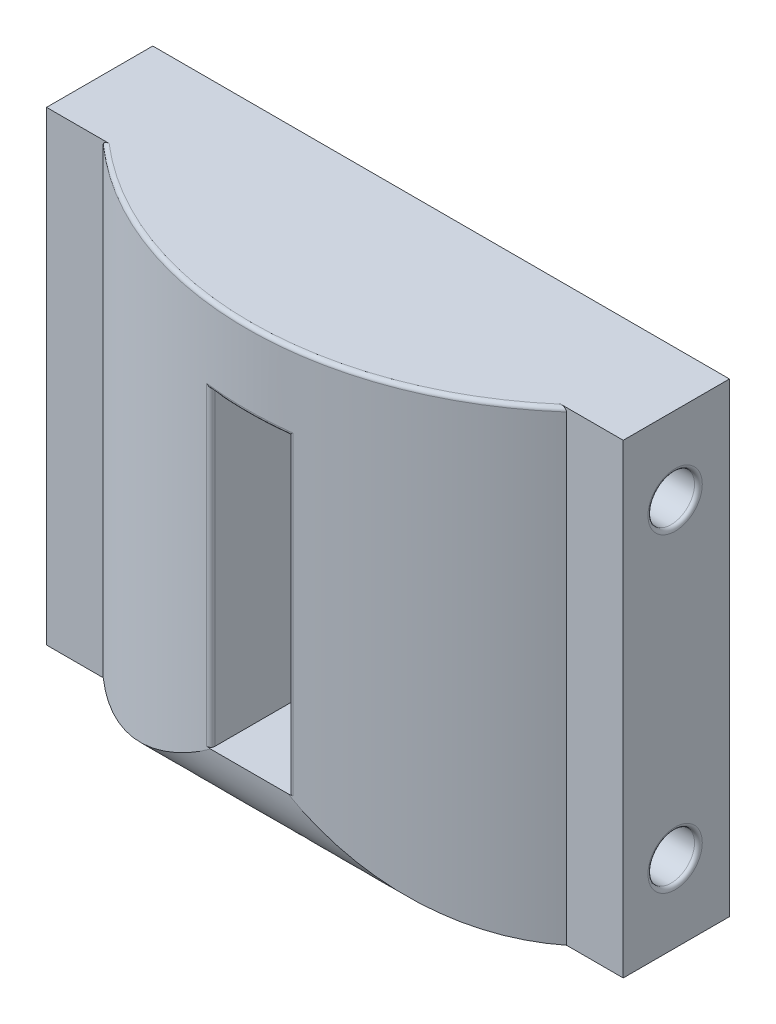
SolidWorks part; units mm, degrees
ref_plane "Front Plane" through (0, 0, 0) normal (0, 0, 1) x (1, 0, 0)
ref_plane "Top Plane" through (0, 0, 0) normal (0, 1, 0) x (1, 0, 0)
ref_plane "Right Plane" through (0, 0, 0) normal (1, 0, 0) x (0, 0, -1)
sketch "Sketch1" plane through (0, 0, 0) normal (0, 0, 1) x (1, 0, 0)
  line L1 (0, 0) -> (29.85, 0)
  line L2 (0, 0) -> (0, 30)
  line L3 (0, 30) -> (29.85, 30)
  line L4 (29.85, 0) -> (29.85, 30)
  dimension "D1" = 29.85
  dimension "D2" = 30
extrude "Boss-Extrude1" add sketch "Sketch1" along normal blind 12.5
sketch "Sketch2" plane through (0, 0, 12.5) normal (0, 0, 1) x (1, 0, 0)
  line L1 (12.425, 25) -> (17.425, 25)
  line L2 (12.425, 25) -> (12.425, 5)
  line L3 (12.425, 5) -> (17.425, 5)
  line L4 (17.425, 25) -> (17.425, 5)
  line L5 (29.85, 30) -> (0, 30) construction
  line L6 (14.925, 30) -> (14.925, 0) construction
  line L7 (0, 0) -> (29.85, 0) construction
  point P4 (14.925, 25)
  dimension "D1" = 5
  dimension "D2" = 20
  dimension "D4" = 5
extrude "Cut-Extrude1" cut sketch "Sketch2" against normal through all
sketch "Sketch4" plane through (29.85, 0, 0) normal (1, 0, 0) x (0, 0, -1)
  line L0 (-12.5, 30) -> (0, 30) construction
  line L1 (0, 0) -> (0, 30) construction
  line L2 (-12.5, 0) -> (0, 0) construction
  circle A0 centre (-3.5, 25) radius 1.5
  circle A1 centre (-3.5, 5) radius 1.5
  dimension "D1" = 3
  dimension "D2" = 5
  dimension "D3" = 5
  dimension "D4" = 3.5
sketch "Sketch5" plane through (0, 0, 0) normal (0, -1, 0) x (1, 0, 0)
  line L0 (0, 12.5) -> (0, 0) construction
  line L1 (29.85, 12.5) -> (29.85, 0) construction
  line L7 (0, 6.8426) -> (-5.7096, 18.3511)
  line L8 (-5.7096, 18.3511) -> (14.925, 23.822)
  line L9 (14.925, 23.822) -> (34.3868, 18.3511)
  line L10 (34.3868, 18.3511) -> (29.85, 6.8426)
  line L11 (0, 12.5) -> (29.85, 12.5) construction
  arc A0 (0, 6.8426) -> (29.85, 6.8426) centre (14.925, -10.0157) cw
  dimension "D1" = 22.5157
extrude "Cut-Extrude3" cut sketch "Sketch5" against normal through all contours L8 L9 L10 A0 L7
sketch "Sketch7" plane through (29.85, 0, 0) normal (1, 0, 0) x (0, 0, -1)
  line L0 (-6.8426, 0) -> (-6.8426, -1.9837)
  line L1 (-6.8426, -1.9837) -> (-14.6013, -1.9837)
  line L2 (-14.6013, -1.9837) -> (-14.6013, 5)
  line L3 (-12.3608, 5) -> (-14.6013, 5)
  spline S0 degree 2 poles (-6.8426, 0) (-11.6861, 0.2988) (-12.3608, 5) knots 0 0 0 1 1 1
extrude "Cut-Extrude5" cut sketch "Sketch7" against normal through all
sketch "Sketch8" plane through (29.85, 0, 0) normal (1, 0, 0) x (0, 0, -1)
  line L1 (-6.8426, 30) -> (0, 30)
  line L2 (-6.8426, 30) -> (-6.8426, 0)
  line L3 (-6.8426, 0) -> (0, 0)
  line L4 (0, 30) -> (0, 0)
extrude "Boss-Extrude5" add sketch "Sketch8" along normal blind 3.65
sketch "Sketch9" plane through (0, 0, 0) normal (-1, 0, 0) x (0, 0, 1)
  line L1 (0, 30) -> (6.8426, 30)
  line L2 (0, 30) -> (0, 0)
  line L3 (0, 0) -> (6.8426, 0)
  line L4 (6.8426, 30) -> (6.8426, 0)
extrude "Boss-Extrude6" add sketch "Sketch9" along normal blind 3.65
extrude "Cut-Extrude7" cut sketch "Sketch4" against normal through all both and the other way through all
fillet "Fillet17" radius 0.25 4 edges at (33.5, 5, 2) (33.5, 25, 2) (-3.65, 5, 2) (-3.65, 25, 2)
fillet "Fillet19" radius 0.25 4 edges at (12.425, 15, 12.3608) (14.925, 25, 12.5) (17.425, 15, 12.3608) (14.925, 30, 12.5)
